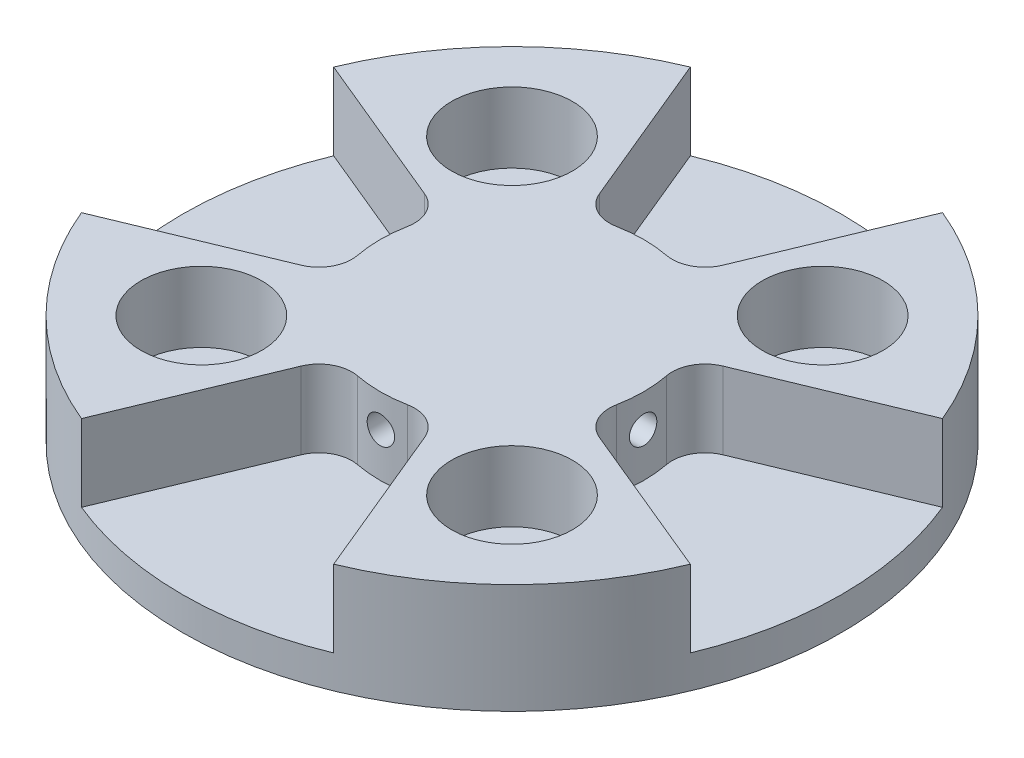
SolidWorks part; units mm, degrees
ref_plane "Front Plane" through (0, 0, 0) normal (0, 0, 1) x (1, 0, 0)
ref_plane "Top Plane" through (0, 0, 0) normal (0, 1, 0) x (1, 0, 0)
ref_plane "Right Plane" through (0, 0, 0) normal (1, 0, 0) x (0, 0, -1)
sketch "Sketch1" plane through (0, 0, 0) normal (0, 1, 0) x (1, 0, 0)
  circle A0 centre (0, 0) radius 30
  dimension "D1" = 60
extrude "Boss-Extrude1" add sketch "Sketch1" along normal blind 10
hole_wizard "CBORE for M6 Hex Socket Head Cap Screw1" positions "Sketch2" profile "Sketch3" counterbore size "M6" standard "ISO" end condition up to next
sketch "Sketch2" plane through (0, 10, 0) normal (0, 1, 0) x (1, 0, 0)
  line L1 (14.1421, 14.1421) -> (-14.1421, 14.1421)
  line L2 (-14.1421, 14.1421) -> (-14.1421, -14.1421)
  line L3 (-14.1421, -14.1421) -> (14.1421, -14.1421)
  line L4 (14.1421, -14.1421) -> (14.1421, 14.1421)
  circle A0 centre (0, 0) radius 20 construction
  point P3 (14.1421, 14.1421)
  point P4 (-14.1421, 14.1421)
  point P5 (-14.1421, -14.1421)
  point P6 (14.1421, -14.1421)
  dimension "D1" = 40
sketch "Sketch3" plane through (14.1421, 10, 14.1421) normal (1, 0, 0) x (0, 0, 1)
  line L0 (0, 0) -> (0, 10)
  line L1 (0, 10) -> (3.3, 10)
  line L3 (3.3, 10) -> (3.3, 6.4)
  line L4 (3.3, 6.4) -> (5.5, 6.4)
  line L5 (5.5, 6.4) -> (5.5, 0)
  line L7 (5.5, 0) -> (0, 0)
  line L11 (0, -6.35) -> (0, 107.95) construction
  dimension "Thru Hole Dia." = 6.6
  dimension "Thru Hole Depth" = 10
  dimension "C'Bore Dia." = 11
  dimension "C'Bore Depth" = 6.4
sketch "Sketch4" plane through (0, 10, 0) normal (0, 1, 0) x (1, 0, 0)
  line L0 (0, 0) -> (-11.4805, -27.7164)
  line L1 (0, 0) -> (11.4805, -27.7164)
  circle A0 centre (0, 0) radius 12
  circle A1 centre (0, 0) radius 30 construction
  circle M8 centre (0, 0) radius 30
  dimension "D1" = 18
  dimension "D2" = 45
extrude "Cut-Extrude1" cut sketch "Sketch4" against normal blind 7 contours A0 L0 L1 M8 region at (0, 10, 21.7173)
ref_plane "Plane1" through (0, 0, 12) normal (0, 0, 1) x (1, 0, 0)
hole_wizard "M3 Tapped Hole1" positions "Sketch5" profile "Sketch6" tap size "M3" standard "ISO"
sketch "Sketch5" plane through (0, 0, 12) normal (0, 0, 1) x (1, 0, 0)
  line L0 (30, 10) -> (-30, 10) construction
  point P0 (0, 7)
  dimension "D1" = 3
sketch "Sketch6" plane through (0, 7, 12) normal (1, 0, 0) x (0, -1, 0)
  line L0 (0, 0) -> (0, 12.7511)
  line L1 (0, 12.7511) -> (1.25, 12)
  line L2 (1.25, 12) -> (1.25, 0)
  line L5 (1.25, 0) -> (0, 0)
  line L10 (0, 12.7511) -> (-1.25, 12) construction
  line L11 (0, -6.35) -> (0, 107.95) construction
  dimension "Tap Drill Dia." = 2.5
  dimension "Tap Drill Depth" = 12
  dimension "Drill Angle" = 118
cosmetic thread "Hole Thread2" parameters "D1"=6, "D2"=3
pattern_circular "CirPattern1" count 4 over 360 about axis through (0, 10, 0) along (0, 1, 0) of "Cut-Extrude1", "M3 Tapped Hole1"
ref_plane "Plane2" through (0, 0, 30) normal (0, 0, 1) x (1, 0, 0)
sketch "Sketch8" plane through (0, 0, 30) normal (0, 0, 1) x (1, 0, 0)
  circle A0 centre (0, 7) radius 3.25
  dimension "D1" = 6.5
extrude "Cut-Extrude2" [suppressed] cut sketch "Sketch8" against normal blind 3.4
fillet "Fillet1" radius 3 8 edges at (4.5922, 6.5, 11.0866) (-4.5922, 6.5, 11.0866) (-11.0866, 6.5, 4.5922) (-11.0866, 6.5, -4.5922) (-4.5922, 6.5, -11.0866) (4.5922, 6.5, -11.0866) (11.0866, 6.5, -4.5922) (11.0866, 6.5, 4.5922)
